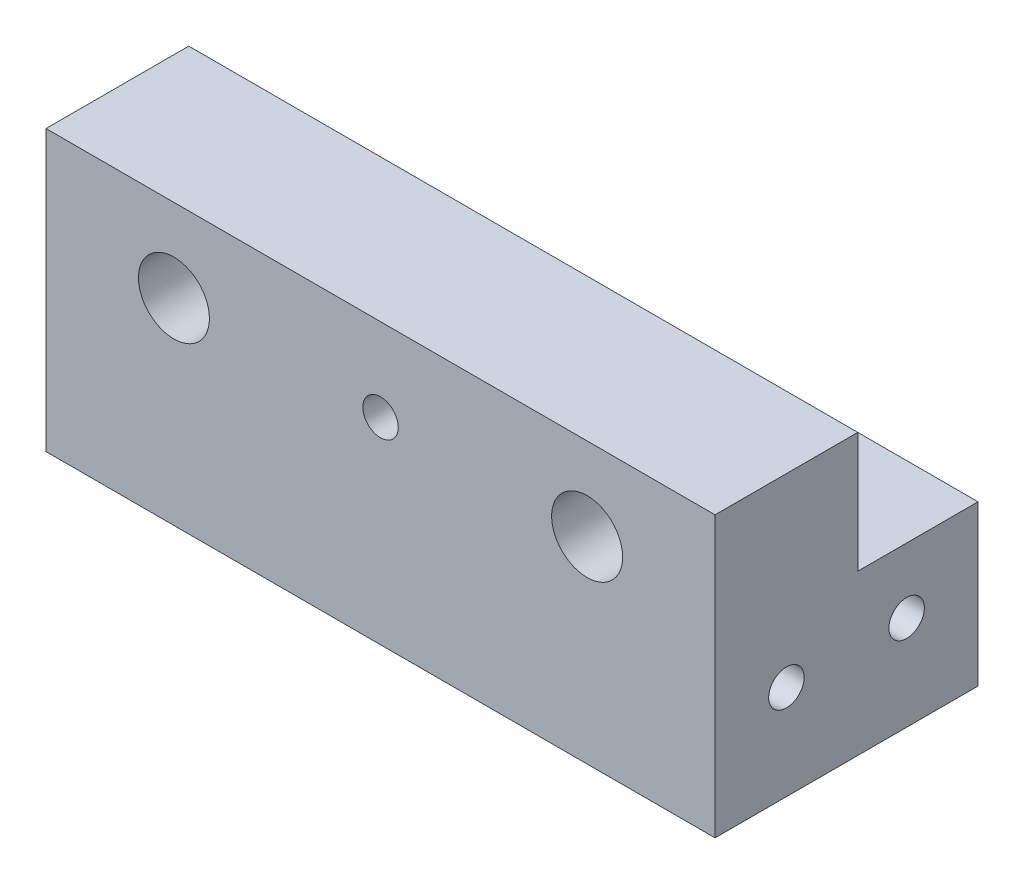
SolidWorks part; units mm, degrees
material "ABS"
ref_plane "X-Y Datum" through (0, 0, 0) normal (0, 0, 1) x (1, 0, 0)
ref_plane "X-Z Datum" through (0, 0, 0) normal (0, 1, 0) x (1, 0, 0)
ref_plane "Y-Z Datum" through (0, 0, 0) normal (1, 0, 0) x (0, 0, -1)
sketch "Sketch1" plane through (0, 0, 0) normal (0, 0, 1) x (1, 0, 0)
  line L1 (-28.275, 11.1125) -> (28.275, 11.1125)
  line L2 (-28.275, 11.1125) -> (-28.275, -11.1125)
  line L3 (-28.275, -11.1125) -> (28.275, -11.1125)
  line L4 (28.275, 11.1125) -> (28.275, -11.1125)
  line L5 (-28.275, 11.1125) -> (28.275, -11.1125) construction
  line L6 (-28.275, -11.1125) -> (28.275, 11.1125) construction
  point P0 (0, 0)
  dimension "D1" = 56.55
  dimension "D2" = 22.225
extrude "Boss-Extrude1" add sketch "Sketch1" along normal blind 22.225 contours L2 L3 L4 L1
sketch "Sketch2" plane through (0, 0, 22.225) normal (0, 0, 1) x (1, 0, 0)
  line L0 (-23.5453, 4.1125) -> (31.0951, 4.1125) construction
  line L1 (0, 11.1125) -> (0, -11.1125) construction
  line L2 (-28.275, 11.1125) -> (28.275, 11.1125) construction
  line L3 (-17.4625, 4.1125) -> (17.4625, 4.1125) construction
  line L4 (-28.275, -11.1125) -> (28.275, -11.1125) construction
  circle A0 centre (17.4625, 4.1125) radius 3
  circle A1 centre (-17.4625, 4.1125) radius 3
  circle A2 centre (0, 4.1125) radius 1.5
  point P10 (0, 4.1125)
  dimension "D1" = 6
  dimension "D4" = 3
  dimension "D2" = 34.925
  dimension "D3" = 7
extrude "Cut-Extrude1" cut sketch "Sketch2" against normal blind 10 contours A1 L0 L3 | L0 A1 L3 | L0 L3 A0 | L3 L0 A0 | A2 region at (17.4625, 4.1125, 22.225) region at (-17.4625, 4.1125, 22.225) region at (0, 4.1125, 22.225)
sketch "Sketch3" plane through (-28.275, 0, 0) normal (-1, 0, 0) x (0, 0, 1)
  line L0 (0, -4.5375) -> (22.225, -4.5375) construction
  line L1 (0, 11.1125) -> (0, -11.1125) construction
  line L2 (22.225, 184.8875) -> (22.225, -15.7125) construction
  line L3 (16.1925, -4.5375) -> (6.0325, -4.5375) construction
  line L4 (11.1125, 11.1125) -> (11.1125, -11.1125) construction
  line L5 (22.225, 11.1125) -> (0, 11.1125) construction
  line L6 (22.225, -11.1125) -> (0, -11.1125) construction
  line L7 (-277.475, -12.5375) -> (22.225, -12.5375) construction
  circle A0 centre (16.1925, -4.5375) radius 1.5
  circle A1 centre (6.0325, -4.5375) radius 1.5
  point P10 (11.1125, -4.5375)
  dimension "D1" = 3
  dimension "D2" = 10.16
  dimension "D3" = 8
extrude "Cut-Extrude2" cut sketch "Sketch3" against normal through all
sketch "Sketch4" plane through (-28.275, 0, 0) normal (-1, 0, 0) x (0, 0, 1)
  line L1 (0, 11.1125) -> (10.16, 11.1125)
  line L2 (0, 11.1125) -> (0, 0.9525)
  line L3 (0, 0.9525) -> (10.16, 0.9525)
  line L4 (10.16, 11.1125) -> (10.16, 0.9525)
  dimension "D1" = 10.16
  dimension "D2" = 10.16
extrude "Cut-Extrude3" cut sketch "Sketch4" against normal through all
sketch "Sketch5" plane through (0, -11.1125, 0) normal (0, -1, 0) x (1, 0, 0)
  line L4 (-28.275, 0) -> (28.275, 0)
  line L5 (28.275, 0) -> (28.275, 22.225)
  line L6 (28.275, 22.225) -> (-28.275, 22.225)
  line L7 (-28.275, 22.225) -> (-28.275, 0)
  line L8 (-28.275, 0) -> (28.275, 0)
  line L9 (28.275, 0) -> (28.275, 22.225)
  line L10 (28.275, 22.225) -> (-28.275, 22.225)
  line L11 (-28.275, 22.225) -> (-28.275, 0)
  dimension "D1" = 0
extrude "Boss-Extrude2" add sketch "Sketch5" along normal blind 1.4249
